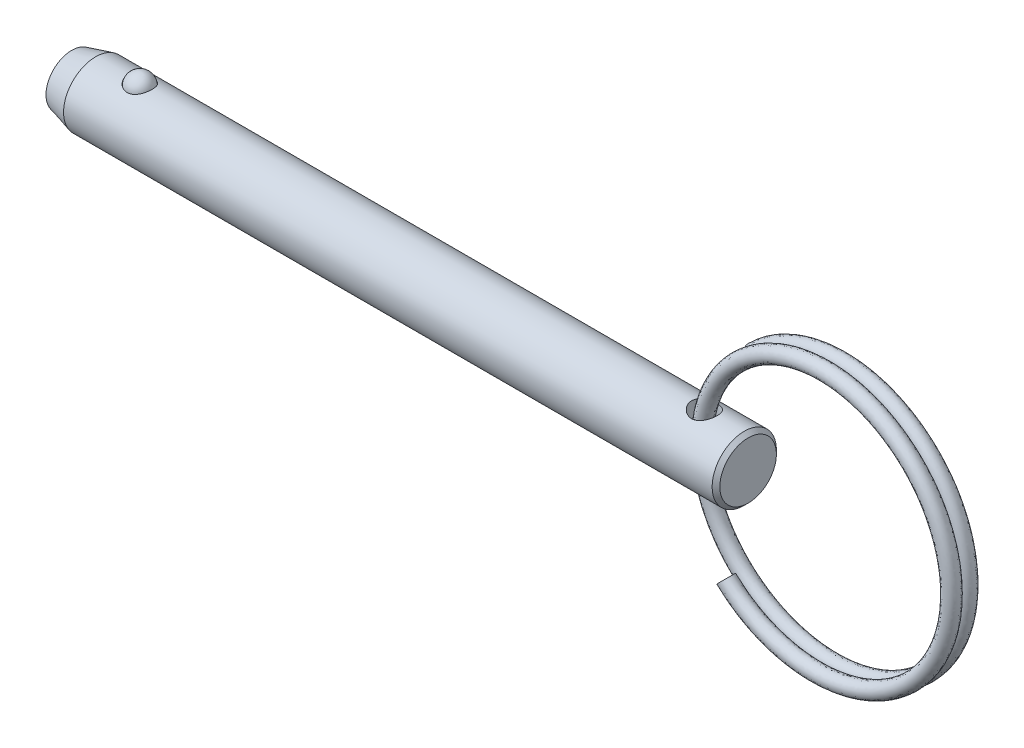
SolidWorks part; units mm, degrees
material "Plain Carbon Steel"
ref_plane "Front" through (0, 0, 0) normal (0, 0, 1) x (1, 0, 0)
ref_plane "Top" through (0, 0, 0) normal (0, 1, 0) x (1, 0, 0)
ref_plane "Right" through (0, 0, 0) normal (1, 0, 0) x (0, 0, -1)
sketch "Sketch1" plane through (0, 0, 0) normal (0, 0, 1) x (1, 0, 0)
  line L0 (33.4264, 2.794) -> (33.0454, 3.175)
  line L1 (33.0454, 3.175) -> (33.4264, 3.175) construction
  line L4 (33.4264, 2.794) -> (33.4264, 0)
  line L5 (33.4264, 3.175) -> (33.4264, 2.794) construction
  line L16 (33.0454, 3.175) -> (-31.0565, 3.175)
  line L17 (-33.4264, 3.175) -> (-33.4264, 2.54) construction
  line L19 (-31.0565, 3.175) -> (-33.4264, 3.175) construction
  line L22 (-33.4264, -3.175) -> (-31.0565, -3.175) construction
  line L23 (-26.6919, 2.8575) -> (-26.6919, -2.8575) construction
  line L24 (-33.4264, 0) -> (33.4264, 0)
  line L27 (33.4264, 0) -> (36.2204, 0) construction
  line L29 (-33.4264, 0) -> (-33.4264, -2.54) construction
  line L36 (27.8384, 0) -> (27.8384, 3.175) construction
  line L37 (-33.4264, 2.54) -> (-33.4264, 0)
  line L38 (-31.0565, -3.175) -> (33.4264, -3.175) construction
  line L39 (-33.4264, -2.54) -> (-33.4264, -3.175) construction
  line L40 (-31.0565, 3.175) -> (-33.4264, 2.54)
  line L42 (-31.0565, -3.175) -> (-33.4264, -2.54) construction
  line L43 (-31.0565, 3.175) -> (-31.0565, -3.175) construction
  circle A2 centre (-26.6919, 2.8575) radius 1.2319 construction
  point P35 (-25.5016, 3.175)
  dimension "A1" = 15
revolve "Revolve1" add sketch "Sketch1" angle 360 about L27
sketch "Sketch2" plane through (0, 0, 0) normal (0, 0, 1) x (1, 0, 0)
  line L0 (-25.4346, 2.8575) -> (-27.9492, 2.8575)
  line L1 (-26.6919, 4.0894) -> (-26.6919, 4.1148) construction
  line L2 (-25.4346, 2.8575) -> (-22.92, 2.8575) construction
  circle A0 centre (-26.6919, 2.8575) radius 1.2319 construction
  circle A1 centre (-26.6919, 2.8575) radius 1.2319 construction
  arc A2 (-27.9492, 2.8575) -> (-25.4346, 2.8575) centre (-26.6919, 2.8575) cw
  dimension "D1" = 0.0254
revolve "Cut-Revolve1" cut sketch "Sketch2" angle 360 about L2
sketch "Sketch3" plane through (0, 0, 0) normal (0, 0, 1) x (1, 0, 0)
  line L0 (-25.46, 2.8575) -> (-27.9238, 2.8575)
  line L1 (-25.46, 2.8575) -> (-22.9962, 2.8575) construction
  circle A0 centre (-26.6919, 2.8575) radius 1.2319 construction
  arc A1 (-25.46, 2.8575) -> (-27.9238, 2.8575) centre (-26.6919, 2.8575) ccw
revolve "Revolve2" add sketch "Sketch3" angle 360 about L1
sketch "Sketch4" plane through (0, 0, 0) normal (0, 0, 1) x (1, 0, 0)
  line L1 (29.1084, -3.175) -> (30.3784, -3.175)
  line L2 (29.1084, -3.175) -> (29.1084, 3.175)
  line L3 (29.1084, 3.175) -> (30.3784, 3.175)
  line L4 (30.3784, -3.175) -> (30.3784, 3.175)
  line L5 (29.1084, -3.175) -> (29.1084, -4.445) construction
  line L6 (30.3784, 3.175) -> (33.4264, 3.175) construction
  line L8 (27.8384, -3.175) -> (27.8384, 3.175) construction
  line L9 (27.8384, 0) -> (29.1084, 0) construction
  line L11 (29.1084, 0) -> (30.3784, 0) construction
  line L12 (33.0454, 3.175) -> (-31.0565, 3.175) construction
  line L14 (-31.0565, -3.175) -> (33.4264, -3.175) construction
  dimension "D1" = 2.54
revolve "Cut-Revolve2" cut sketch "Sketch4" angle 360 about L2
sketch "Sketch5" plane through (0, 0, 0) normal (0, 0, 1) x (1, 0, 0)
  line L0 (0, 0) -> (28.1314, 0) construction
  line L1 (28.1314, 0) -> (28.1314, 3.175) construction
  line L2 (33.0454, 3.175) -> (-31.0565, 3.175) construction
  line L3 (41.5934, 0) -> (55.0554, 0) construction
  line L4 (30.3784, 3.175) -> (30.0854, 3.175) construction
  line L5 (29.1084, 3.175) -> (30.3784, 3.175) construction
  line L6 (28.5112, 3.175) -> (28.5112, -3.175) construction
  line L7 (28.1314, 3.175) -> (27.8384, 3.175) construction
  line L8 (29.1084, -3.175) -> (30.3784, -3.175) construction
  line L9 (28.5112, -3.175) -> (30.3784, -3.175) construction
  line L10 (28.1314, 0) -> (41.5934, 0) construction
  line L12 (30.0854, 3.175) -> (28.5112, 3.175) construction
  line L13 (41.5934, 11.938) -> (41.5934, 13.462) construction
  circle A0 centre (41.5934, 0) radius 13.462
  circle A1 centre (41.5934, 0) radius 11.938 construction
  circle A2 centre (41.5934, 0) radius 12.7 construction
  point P26 (41.5934, 12.7)
curve "Helix/Spiral1" pitch 1.5494 height 1.3557 radius 13.462 left hand yes centre (41.5934, 0, 0) axis (0, 0, -1) start towards (-1, 0, 0)
sketch "Sketch6" plane through (114.0038, 0, 0) normal (0, 1, 0) x (0, 0, -1)
  line L0 (0, 84.3484) -> (0, 85.1104) construction
  line L1 (0, 85.1104) -> (0, 85.8724) construction
  circle A0 centre (0, 85.1104) radius 0.762
  dimension "D1" = 1.524
sketch "Sketch7" plane through (0, 0, 0) normal (0, 0, 1) x (1, 0, 0)
  circle A0 centre (41.5934, 0) radius 13.462 construction
  circle A1 centre (41.5934, 0) radius 13.462
curve "Helix/Spiral2" pitch 1.5494 height 1.3557 radius 13.462 left hand yes centre (41.5934, 0, 0) axis (0, 0, 1) start towards (1, 0, 0)
sweep "Sweep1" add profiles "Sketch6" path "Helix/Spiral1"
sweep "Sweep2" add profiles "Sketch6<2>" path "Helix/Spiral2"
sketch "Sketch6<2>" plane through (114.0038, 0, 0) normal (0, 1, 0) x (0, 0, -1) same geometry as "Sketch6"
equation "\"D12@Sketch1\"=\"A@Sketch1\" * 0.80"
equation "\"D2@Sketch1\"=\"A@Sketch1\" * 0.9"
equation "\"D1@Sketch4\" = \"A@Sketch1\" / 2.5"
equation "\"Ring OD@Sketch5\" = \"R Ring Dia@Sketch5\" * 0.06"
equation "\"D4@Helix/Spiral1\"=\"Ring OD@Sketch5\" + 0.001"
equation "\"D1@Sketch6\"=\"Ring OD@Sketch5\""
equation "\"D4@Helix/Spiral2\" = \"D4@Helix/Spiral1\""
equation "\"D5@Helix/Spiral2\" = \"D5@Helix/Spiral1\""
